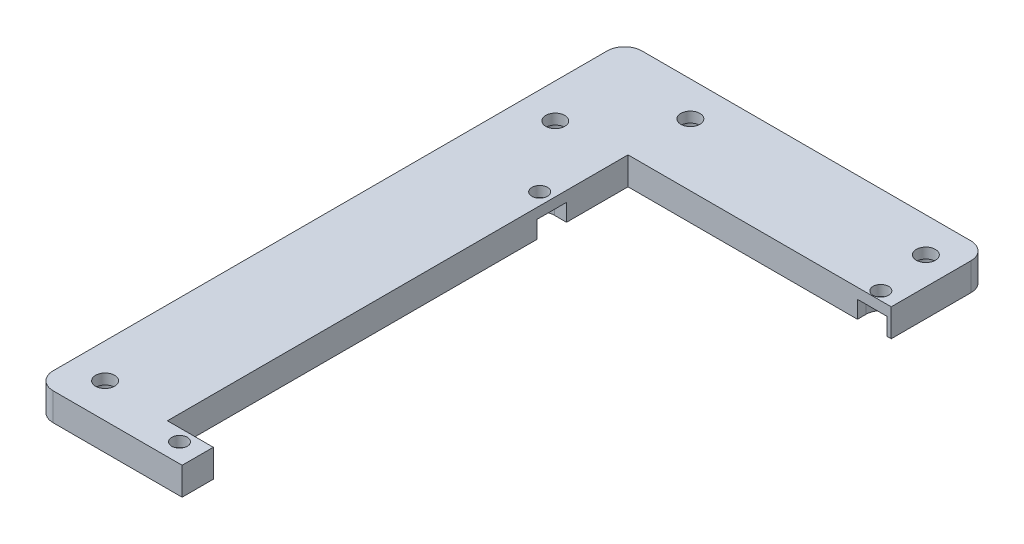
SolidWorks part; units mm, degrees
ref_plane "Front Plane" through (0, 0, 0) normal (0, 0, 1) x (1, 0, 0)
ref_plane "Top Plane" through (0, 0, 0) normal (0, 1, 0) x (1, 0, 0)
ref_plane "Right Plane" through (0, 0, 0) normal (1, 0, 0) x (0, 0, -1)
sketch "Sketch2" plane through (0, 0, 0) normal (0, 1, 0) x (1, 0, 0)
  line L1 (-47.5, -85) -> (52.5, -85)
  line L2 (-52.5, -80) -> (-52.5, 80)
  line L3 (-47.5, 85) -> (47.5, 85)
  line L4 (52.5, -85) -> (52.5, 80)
  line L5 (-52.5, -85) -> (52.5, 85) construction
  line L6 (-52.5, 85) -> (52.5, -85) construction
  line L7 (-23.5, 57) -> (52.5, 57)
  line L8 (-23.5, 57) -> (-23.5, -76)
  line L9 (-23.5, -85) -> (52.5, -85)
  line L10 (52.5, 57) -> (52.5, -85)
  line L11 (-23.5, -76) -> (-10.25, -76)
  line L12 (-23.5, -76) -> (-23.5, -62.4287)
  line L14 (-10.25, -76) -> (-10.25, -85)
  arc A0 (-47.5, -85) -> (-52.5, -80) centre (-47.5, -80) cw
  arc A1 (47.5, 85) -> (52.5, 80) centre (47.5, 80) cw
  arc A2 (-52.5, 80) -> (-47.5, 85) centre (-47.5, 80) cw
  circle A3 centre (-42.5, -75) radius 2.75
  circle A4 centre (-16.5, -79.5) radius 2.25
  circle A5 centre (-27, 35) radius 2.25
  circle A6 centre (47, 59.5) radius 2.25
  circle A7 centre (-23.5, 75) radius 2.75
  circle A8 centre (-42.5, 55) radius 2.75
  circle A9 centre (44.5, 75) radius 2.75
  point P0 (0, 0)
  point P23 (0, 0)
  point P27 (0, 0)
  point P38 (-66.8625, 26.1383)
  dimension "D3" = 5
  dimension "D4" = 10
  dimension "D12" = 10
  dimension "D18" = 25.5
  dimension "D1" = 170
  dimension "D2" = 105
  dimension "D5" = 10
  dimension "D6" = 36
  dimension "D7" = 5.5
  dimension "D8" = 28
  dimension "D9" = 29
  dimension "D10" = 13.25
  dimension "D11" = 9
  dimension "D13" = 30
  dimension "D14" = 10
  dimension "D15" = 29
  dimension "D16" = 10
  dimension "D17" = 8
  dimension "D19" = 50
  dimension "D20" = 25.5
  dimension "D21" = 5.5
extrude "Boss-Extrude1" add sketch "Sketch2" along normal blind 4 and the other way blind 4 contours A2 L2 A0 L1 L14 L11 L8 L7 L4 A1 L3 A9 A8 A7 A6 A5 A4 A3 region at (-49.6226, 0, 82.1226)
sketch "Sketch3" plane through (0, -4, 0) normal (0, -1, 0) x (1, 0, 0)
  line L0 (-27, -30.75) -> (-23.5, -30.75)
  line L1 (-23.5, -57) -> (-23.5, 76) construction
  line L2 (-27, -39.25) -> (-23.5, -39.25)
  line L3 (51.25, -59.5) -> (51.25, -57)
  line L4 (-23.5, -57) -> (52.5, -57) construction
  line L5 (51.25, -57) -> (42.75, -57)
  line L6 (42.75, -57) -> (42.75, -59.5)
  line L7 (-12.25, 79.5) -> (-12.25, 76)
  line L8 (-23.5, 76) -> (-10.25, 76) construction
  line L9 (-12.25, 76) -> (-20.75, 76)
  line L10 (-20.75, 76) -> (-20.75, 79.5)
  line L11 (-23.5, -39.25) -> (-23.5, -30.75)
  circle A0 centre (-23.5, -75) radius 4.25
  circle A1 centre (-42.5, -55) radius 4.25
  arc A2 (-27, -30.75) -> (-27, -39.25) centre (-27, -35) ccw
  circle A3 centre (-42.5, 75) radius 4.25
  arc A4 (-12.25, 79.5) -> (-20.75, 79.5) centre (-16.5, 79.5) ccw
  circle A5 centre (44.5, -75) radius 4.25
  arc A6 (42.75, -59.5) -> (51.25, -59.5) centre (47, -59.5) ccw
  circle A7 centre (-42.5, -55) radius 2.75 construction
  circle A8 centre (-27, -35) radius 2.25 construction
  circle A9 centre (-42.5, 75) radius 2.75 construction
  circle A10 centre (-16.5, 79.5) radius 2.25 construction
  circle A11 centre (44.5, -75) radius 2.75 construction
  circle A12 centre (47, -59.5) radius 2.25 construction
extrude "Cut-Extrude1" cut sketch "Sketch3" against normal blind 5 contours A0 | A5 | A6 L3 L5 L6 | L0 L11 L2 A2 | A1 | A4 L10 L9 L7 | A3
